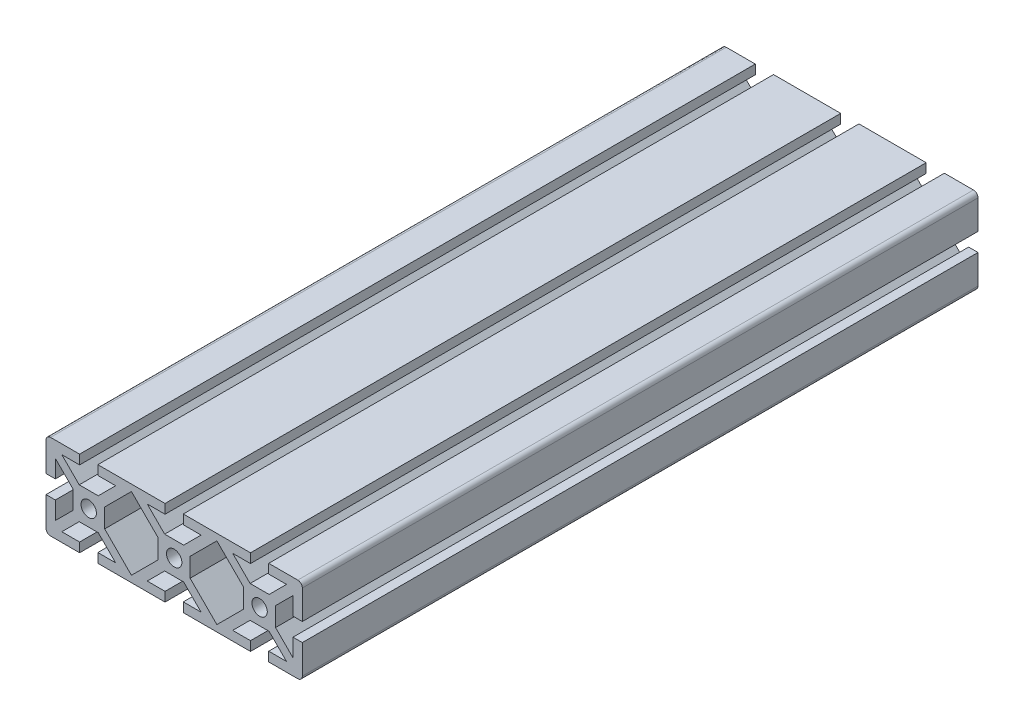
SolidWorks part; units mm, degrees
ref_plane "Front"
ref_plane "Top" through (0, 0, 0) normal (0, 1, 0) x (1, 0, 0)
ref_plane "Right" through (0, 0, 0) normal (1, 0, 0) x (0, 0, -1)
sketch "Sketch1" plane through (0, 0, 0) normal (0, 0, 1) x (1, 0, 0)
  line L0 (0, 0) -> (0, 23.7337) construction
  line L1 (-34.036, -19.05) -> (-34.036, -14.8844)
  line L2 (-45.212, -4.2383) -> (-45.212, 4.2383)
  line L3 (-45.212, 4.2383) -> (-52.9844, 12.0107)
  line L4 (-52.9844, 4.064) -> (-52.9844, 12.0107)
  line L5 (-55.118, 19.05) -> (-42.164, 19.05)
  line L6 (-57.15, 4.064) -> (-57.15, 17.018)
  line L7 (-33.8617, 7.112) -> (-42.3383, 7.112)
  line L8 (-42.3383, 7.112) -> (-50.1107, 14.8844)
  line L9 (-50.1107, 14.8844) -> (-42.164, 14.8844)
  line L10 (-33.8617, 7.112) -> (-26.0893, 14.8844)
  line L11 (-26.0893, 14.8844) -> (-34.036, 14.8844)
  line L12 (-42.164, 19.05) -> (-42.164, 14.8844)
  line L13 (-4.064, 19.05) -> (-34.036, 19.05)
  line L14 (-7.112, 4.2383) -> (-19.05, 16.1763)
  line L15 (-30.988, 4.2383) -> (-19.05, 16.1763)
  line L16 (4.2383, 7.112) -> (-4.2383, 7.112)
  line L17 (-30.988, 4.2383) -> (-30.988, -4.2383)
  line L18 (0, 0) -> (-57.3277, 0) construction
  line L19 (-52.9844, -4.064) -> (-57.15, -4.064)
  line L20 (-4.2383, 7.112) -> (-12.0107, 14.8844)
  line L21 (-4.064, -19.05) -> (-4.064, -14.8844)
  line L22 (-12.0107, 14.8844) -> (-4.064, 14.8844)
  line L23 (-12.0107, -14.8844) -> (-4.064, -14.8844)
  line L24 (-4.2383, -7.112) -> (-12.0107, -14.8844)
  line L25 (4.2383, -7.112) -> (-4.2383, -7.112)
  line L26 (-30.988, -4.2383) -> (-19.05, -16.1763)
  line L27 (-7.112, -4.2383) -> (-19.05, -16.1763)
  line L28 (-4.064, -19.05) -> (-34.036, -19.05)
  line L29 (-42.164, -19.05) -> (-42.164, -14.8844)
  line L30 (-26.0893, -14.8844) -> (-34.036, -14.8844)
  line L31 (-33.8617, -7.112) -> (-26.0893, -14.8844)
  line L32 (-50.1107, -14.8844) -> (-42.164, -14.8844)
  line L33 (-42.3383, -7.112) -> (-50.1107, -14.8844)
  line L34 (-33.8617, -7.112) -> (-42.3383, -7.112)
  line L35 (-4.064, 19.05) -> (-4.064, 14.8844)
  line L36 (-57.15, -4.064) -> (-57.15, -17.018)
  line L37 (-7.112, 4.2383) -> (-7.112, -4.2383)
  line L38 (-55.118, -19.05) -> (-42.164, -19.05)
  line L39 (-52.9844, -4.064) -> (-52.9844, -12.0107)
  line L40 (-45.212, -4.2383) -> (-52.9844, -12.0107)
  line L41 (34.036, 19.05) -> (34.036, 14.8844)
  line L42 (52.9844, 4.064) -> (57.15, 4.064)
  line L43 (45.212, -4.2383) -> (52.9844, -12.0107)
  line L44 (52.9844, -4.064) -> (52.9844, -12.0107)
  line L45 (55.118, -19.05) -> (42.164, -19.05)
  line L46 (7.112, 4.2383) -> (7.112, -4.2383)
  line L47 (57.15, -4.064) -> (57.15, -17.018)
  line L48 (4.064, 19.05) -> (4.064, 14.8844)
  line L49 (33.8617, -7.112) -> (42.3383, -7.112)
  line L50 (42.3383, -7.112) -> (50.1107, -14.8844)
  line L51 (50.1107, -14.8844) -> (42.164, -14.8844)
  line L52 (33.8617, -7.112) -> (26.0893, -14.8844)
  line L53 (26.0893, -14.8844) -> (34.036, -14.8844)
  line L54 (42.164, -19.05) -> (42.164, -14.8844)
  line L55 (4.064, -19.05) -> (34.036, -19.05)
  line L56 (7.112, -4.2383) -> (19.05, -16.1763)
  line L57 (30.988, -4.2383) -> (19.05, -16.1763)
  line L58 (4.2383, -7.112) -> (12.0107, -14.8844)
  line L59 (12.0107, -14.8844) -> (4.064, -14.8844)
  line L60 (-52.9844, 4.064) -> (-57.15, 4.064)
  line L61 (-34.036, 19.05) -> (-34.036, 14.8844)
  line L62 (12.0107, 14.8844) -> (4.064, 14.8844)
  line L63 (4.064, -19.05) -> (4.064, -14.8844)
  line L64 (4.2383, 7.112) -> (12.0107, 14.8844)
  line L65 (52.9844, -4.064) -> (57.15, -4.064)
  line L66 (30.988, 4.2383) -> (30.988, -4.2383)
  line L67 (30.988, 4.2383) -> (19.05, 16.1763)
  line L68 (7.112, 4.2383) -> (19.05, 16.1763)
  line L69 (4.064, 19.05) -> (34.036, 19.05)
  line L70 (42.164, 19.05) -> (42.164, 14.8844)
  line L71 (26.0893, 14.8844) -> (34.036, 14.8844)
  line L72 (33.8617, 7.112) -> (26.0893, 14.8844)
  line L73 (50.1107, 14.8844) -> (42.164, 14.8844)
  line L74 (42.3383, 7.112) -> (50.1107, 14.8844)
  line L75 (33.8617, 7.112) -> (42.3383, 7.112)
  line L76 (57.15, 4.064) -> (57.15, 17.018)
  line L77 (55.118, 19.05) -> (42.164, 19.05)
  line L78 (52.9844, 4.064) -> (52.9844, 12.0107)
  line L79 (45.212, 4.2383) -> (52.9844, 12.0107)
  line L80 (45.212, -4.2383) -> (45.212, 4.2383)
  line L81 (34.036, -19.05) -> (34.036, -14.8844)
  arc A0 (-55.118, 19.05) -> (-57.15, 17.018) centre (-55.118, 17.018) ccw
  arc A1 (-55.118, -19.05) -> (-57.15, -17.018) centre (-55.118, -17.018) cw
  circle A2 centre (38.1, 0) radius 3.429
  arc A3 (55.118, -19.05) -> (57.15, -17.018) centre (55.118, -17.018) ccw
  circle A4 centre (-38.1, 0) radius 3.429
  circle A5 centre (0, 0) radius 3.429
  arc A6 (55.118, 19.05) -> (57.15, 17.018) centre (55.118, 17.018) cw
  point P31 (-7.112, 0)
  point P36 (0, 7.112)
  point P39 (-30.988, 0)
  point P40 (0, 7.112)
  point P50 (-45.212, 0)
  point P66 (-7.112, 0)
  point P85 (0, -7.112)
  point P89 (-30.988, 0)
  point P91 (0, 7.112)
  point P99 (-45.212, 0)
  point P107 (45.212, 0)
  point P108 (30.988, 0)
  point P109 (7.112, 0)
  dimension "D2" = 4.064
  dimension "D5" = 57.15
  dimension "D6" = 45
  dimension "D13" = 4.1656
  dimension "D15" = 4.2383
  dimension "D4" = 42.164
  dimension "D11" = 45.212
  dimension "D12" = 4.1656
  dimension "D14" = 4.2383
  dimension "D3" = 34.036
  dimension "D22" = 2.032
  dimension "D24" = 6.858
  dimension "D1" = 19.05
  dimension "D7" = 45
  dimension "D8" = 45
  dimension "D9" = 7.112
  dimension "D10" = 30.988
  dimension "D16" = 11.938
  dimension "D17" = 4.064
  dimension "D18" = 4.064
  dimension "D19" = 4.064
  dimension "D20" = 4.2383
  dimension "D21" = 14.986
  dimension "D23" = 38.1
extrude "FinalCut" add sketch "Sketch1" against normal blind 301.3074
ref_plane "A" through (0, 0, 0) normal (0, 0, 1) x (1, 0, 0)
ref_plane "B" through (0, 0, -301.3074) normal (0, 0, -1) x (-1, 0, 0)
ref_plane "Y+" through (0, 19.05, 0) normal (0, 1, 0) x (-1, 0, 0)
ref_plane "X+" through (57.15, 0, 0) normal (1, 0, 0) x (0, 0, -1)
ref_plane "Y-" through (0, -19.05, 0) normal (0, -1, 0) x (1, 0, 0)
ref_plane "X-" through (-57.15, 0, 0) normal (-1, 0, 0) x (0, 0, 1)
ref_plane "Slot-1-7-" through (-38.1, 0, 0) normal (1, 0, 0) x (0, 1, 0)
ref_plane "Slot-2-6-" through (0, 0, 0) normal (1, 0, 0) x (0, 0, -1)
ref_plane "Slot-3-5-" through (38.1, 0, 0) normal (1, 0, 0) x (0, 1, 0)
ref_plane "Slot-4-8-" through (0, 0, 0) normal (0, 1, 0) x (0, 0, -1)
sketch "Sketch2" plane through (0, 19.05, 0) normal (0, 1, 0) x (-1, 0, 0)
  circle A0 centre (38.1, -21.717) radius 10.3124
  dimension "D1" = 38.1
  dimension "D2" = 21.717
  dimension "D3" = 20.6248
extrude "AFA1" [suppressed] cut sketch "Sketch2"
sketch "Sketch59" plane through (0, 19.05, 0) normal (0, 1, 0) x (-1, 0, 0)
  line L0 (4.064, 0) -> (34.036, 0) construction
  circle A0 centre (0, -21.717) radius 10.3124
  dimension "D1" = 20.6248
  dimension "D2" = 21.717
extrude "AFA2" [suppressed] cut sketch "Sketch59"
sketch "Sketch4" plane through (0, 19.05, 0) normal (0, 1, 0) x (-1, 0, 0)
  line L2 (-34.036, 0) -> (-4.064, 0) construction
  circle A0 centre (-38.1, -21.717) radius 10.3124
  dimension "D1" = 38.1
  dimension "D2" = 20.6248
  dimension "D3" = 21.717
extrude "AFA3" [suppressed] cut sketch "Sketch4"
sketch "Sketch5" plane through (57.15, 0, 0) normal (1, 0, 0) x (0, 0, -1)
  circle A0 centre (21.717, 0) radius 10.3124
  dimension "D1" = 20.6248
  dimension "D2" = 21.717
extrude "AFA4" [suppressed] cut sketch "Sketch5"
sketch "Sketch7" plane through (0, -19.05, 0) normal (0, -1, 0) x (1, 0, 0)
  circle A0 centre (38.1, -21.717) radius 10.3124
  dimension "D1" = 38.1
  dimension "D2" = 21.717
  dimension "D3" = 20.6248
extrude "AFA5" [suppressed] cut sketch "Sketch7"
sketch "Sketch61" plane through (0, -19.05, 0) normal (0, -1, 0) x (1, 0, 0)
  circle A0 centre (0, -21.717) radius 10.3124
  dimension "D1" = 21.717
  dimension "D2" = 20.6248
extrude "AFA6" [suppressed] cut sketch "Sketch61"
sketch "Sketch8" plane through (0, -19.05, 0) normal (0, -1, 0) x (1, 0, 0)
  circle A0 centre (-38.1, -21.717) radius 10.3124
  dimension "D1" = 38.1
  dimension "D2" = 21.717
  dimension "D3" = 20.6248
extrude "AFA7" [suppressed] cut sketch "Sketch8"
sketch "Sketch10" plane through (-57.15, 0, 0) normal (-1, 0, 0) x (0, 0, 1)
  circle A0 centre (-21.717, 0) radius 10.3124
  dimension "D1" = 21.717
  dimension "D2" = 20.6248
extrude "AFA8" [suppressed] cut sketch "Sketch10"
sketch "Sketch12" plane through (0, 19.05, 0) normal (0, 1, 0) x (-1, 0, 0)
  line L1 (4.064, -301.3074) -> (34.036, -301.3074) construction
  circle A0 centre (38.1, -279.5904) radius 10.3124
  dimension "D1" = 21.717
  dimension "D2" = 38.1
  dimension "D3" = 20.6248
extrude "AFB1" [suppressed] cut sketch "Sketch12"
sketch "Sketch60" plane through (0, 19.05, 0) normal (0, 1, 0) x (-1, 0, 0)
  line L0 (4.064, -301.3074) -> (34.036, -301.3074) construction
  circle A0 centre (0, -279.5904) radius 10.3124
  dimension "D1" = 20.6248
  dimension "D2" = 21.717
extrude "AFB2" [suppressed] cut sketch "Sketch60"
sketch "Sketch11" plane through (0, 19.05, 0) normal (0, 1, 0) x (-1, 0, 0)
  line L1 (-34.036, -301.3074) -> (-4.064, -301.3074) construction
  circle A0 centre (-38.1, -279.5904) radius 10.3124
  dimension "D1" = 38.1
  dimension "D2" = 20.6248
  dimension "D3" = 21.717
extrude "AFB3" [suppressed] cut sketch "Sketch11"
sketch "Sketch14" plane through (57.15, 0, 0) normal (1, 0, 0) x (0, 0, -1)
  line L7 (301.3074, -17.018) -> (301.3074, -4.064) construction
  circle A0 centre (279.5904, 0) radius 10.3124
  dimension "D1" = 21.717
  dimension "D2" = 20.6248
extrude "AFB4" [suppressed] cut sketch "Sketch14"
sketch "Sketch15" plane through (0, -19.05, 0) normal (0, -1, 0) x (1, 0, 0)
  line L1 (4.064, -301.3074) -> (34.036, -301.3074) construction
  circle A0 centre (38.1, -279.5904) radius 10.3124
  dimension "D1" = 21.717
  dimension "D2" = 38.1
  dimension "D3" = 20.6248
extrude "AFB5" [suppressed] cut sketch "Sketch15"
sketch "Sketch62" plane through (0, -19.05, 0) normal (0, -1, 0) x (1, 0, 0)
  line L0 (4.064, -301.3074) -> (34.036, -301.3074) construction
  circle A0 centre (0, -279.5904) radius 10.3124
  dimension "D1" = 20.6248
  dimension "D2" = 21.717
extrude "AFB6" [suppressed] cut sketch "Sketch62"
sketch "Sketch16" plane through (0, -19.05, 0) normal (0, -1, 0) x (1, 0, 0)
  line L1 (-34.036, -301.3074) -> (-4.064, -301.3074) construction
  circle A0 centre (-38.1, -279.5904) radius 10.3124
  dimension "D1" = 21.717
  dimension "D2" = 38.1
  dimension "D3" = 20.6248
extrude "AFB7" [suppressed] cut sketch "Sketch16"
sketch "Sketch17" plane through (-57.15, 0, 0) normal (-1, 0, 0) x (0, 0, 1)
  line L1 (-301.3074, 17.018) -> (-301.3074, 4.064) construction
  circle A0 centre (-279.5904, 0) radius 10.3124
  dimension "D1" = 21.717
  dimension "D2" = 20.6248
extrude "AFB8" [suppressed] cut sketch "Sketch17"
sketch "Sketch20" plane through (0, 19.05, 0) normal (0, 1, 0) x (-1, 0, 0)
  line L1 (4.064, 0) -> (34.036, 0) construction
  circle A0 centre (38.1, -18.3134) radius 10.3124
  dimension "D1" = 18.3134
  dimension "D2" = 20.6248
  dimension "D3" = 38.1
extrude "BFA1" [suppressed] cut sketch "Sketch20"
sketch "Sketch63" plane through (0, 19.05, 0) normal (0, 1, 0) x (-1, 0, 0)
  line L1 (4.064, 0) -> (34.036, 0) construction
  circle A0 centre (0, -18.3134) radius 10.3124
  dimension "D1" = 18.3134
  dimension "D2" = 20.6248
extrude "BFA2" [suppressed] cut sketch "Sketch63"
sketch "Sketch18" plane through (0, 19.05, 0) normal (0, 1, 0) x (-1, 0, 0)
  circle A0 centre (-38.1, -18.3134) radius 10.3124
  dimension "D1" = 38.1
  dimension "D2" = 18.3134
  dimension "D3" = 20.6248
extrude "BFA3" [suppressed] cut sketch "Sketch18"
sketch "Sketch21" plane through (57.15, 0, 0) normal (1, 0, 0) x (0, 0, -1)
  circle A0 centre (18.3134, 0) radius 10.3124
  dimension "D1" = 18.3134
  dimension "D2" = 20.6248
extrude "BFA4" [suppressed] cut sketch "Sketch21"
sketch "Sketch22" plane through (0, -19.05, 0) normal (0, -1, 0) x (1, 0, 0)
  circle A0 centre (38.1, -18.3134) radius 10.3124
  dimension "D2" = 38.1
  dimension "D3" = 20.6248
  dimension "D1" = 18.3134
extrude "BFA5" [suppressed] cut sketch "Sketch22"
sketch "Sketch65" plane through (0, -19.05, 0) normal (0, -1, 0) x (1, 0, 0)
  circle A0 centre (0, -18.3134) radius 10.3124
  dimension "D1" = 20.6248
  dimension "D2" = 18.3134
extrude "BFA6" [suppressed] cut sketch "Sketch65"
sketch "Sketch23" plane through (0, -19.05, 0) normal (0, -1, 0) x (1, 0, 0)
  line L1 (-34.036, 0) -> (-4.064, 0) construction
  circle A0 centre (-38.1, -18.3134) radius 10.3124
  dimension "D1" = 18.3134
  dimension "D2" = 20.6248
  dimension "D3" = 38.1
extrude "BFA7" [suppressed] cut sketch "Sketch23"
sketch "Sketch24" plane through (-57.15, 0, 0) normal (-1, 0, 0) x (0, 0, 1)
  circle A0 centre (-18.3134, 0) radius 10.3124
  dimension "D1" = 18.3134
  dimension "D2" = 20.6248
extrude "BFA8" [suppressed] cut sketch "Sketch24"
sketch "Sketch27" plane through (0, 19.05, 0) normal (0, 1, 0) x (-1, 0, 0)
  line L1 (4.064, -301.3074) -> (34.036, -301.3074) construction
  circle A0 centre (38.1, -282.994) radius 10.3124
  dimension "D1" = 38.1
  dimension "D2" = 20.6248
  dimension "D3" = 18.3134
extrude "BFB1" [suppressed] cut sketch "Sketch27"
sketch "Sketch64" plane through (0, 19.05, 0) normal (0, 1, 0) x (-1, 0, 0)
  line L0 (4.064, -301.3074) -> (34.036, -301.3074) construction
  circle A0 centre (0, -282.994) radius 10.3124
  dimension "D1" = 20.6248
  dimension "D2" = 18.3134
extrude "BFB2" [suppressed] cut sketch "Sketch64"
sketch "Sketch25" plane through (0, 19.05, 0) normal (0, 1, 0) x (-1, 0, 0)
  line L1 (-34.036, -301.3074) -> (-4.064, -301.3074) construction
  circle A0 centre (-38.1, -282.994) radius 10.3124
  dimension "D1" = 18.3134
  dimension "D2" = 38.1
  dimension "D3" = 20.6248
extrude "BFB3" [suppressed] cut sketch "Sketch25"
sketch "Sketch29" plane through (57.15, 0, 0) normal (1, 0, 0) x (0, 0, -1)
  line L1 (301.3074, -17.018) -> (301.3074, -4.064) construction
  circle A0 centre (282.994, 0) radius 10.3124
  dimension "D1" = 18.3134
  dimension "D2" = 20.6248
extrude "BFB4" [suppressed] cut sketch "Sketch29"
sketch "Sketch30" plane through (0, -19.05, 0) normal (0, -1, 0) x (1, 0, 0)
  line L1 (4.064, -301.3074) -> (34.036, -301.3074) construction
  circle A0 centre (38.1, -282.994) radius 10.3124
  dimension "D1" = 18.3134
  dimension "D2" = 38.1
  dimension "D3" = 20.6248
extrude "BFB5" [suppressed] cut sketch "Sketch30"
sketch "Sketch66" plane through (0, -19.05, 0) normal (0, -1, 0) x (1, 0, 0)
  line L0 (-4.2383, -301.3074) -> (4.2383, -301.3074) construction
  circle A0 centre (0, -282.994) radius 10.3124
  dimension "D1" = 18.3134
  dimension "D2" = 20.6248
extrude "BFB6" [suppressed] cut sketch "Sketch66"
sketch "Sketch31" plane through (0, -19.05, 0) normal (0, -1, 0) x (1, 0, 0)
  line L1 (4.064, -301.3074) -> (34.036, -301.3074) construction
  circle A0 centre (-38.1, -282.994) radius 10.3124
  dimension "D1" = 18.3134
  dimension "D2" = 38.1
  dimension "D3" = 20.6248
extrude "BFB7" [suppressed] cut sketch "Sketch31"
sketch "Sketch32" plane through (-57.15, 0, 0) normal (-1, 0, 0) x (0, 0, 1)
  line L5 (-301.3074, -4.064) -> (-301.3074, -17.018) construction
  circle A0 centre (-282.994, 0) radius 10.3124
  dimension "D1" = 18.3134
  dimension "D2" = 20.6248
extrude "BFB8" [suppressed] cut sketch "Sketch32"
sketch "Sketch33" plane through (0, 0, 0) normal (0, 0, 1) x (1, 0, 0)
  circle A0 centre (-38.1, 0) radius 3.937
  circle A1 centre (38.1, 0) radius 3.937
  circle A2 centre (0, 0) radius 3.937
  dimension "D1" = 7.874
extrude "TPA660010" [suppressed] cut sketch "Sketch33"
sketch "Sketch34" plane through (0, 0, -301.3074) normal (0, 0, -1) x (-1, 0, 0)
  circle A0 centre (-38.1, 0) radius 3.937
  circle A1 centre (38.1, 0) radius 3.937
  circle A2 centre (0, 0) radius 3.937
  dimension "D1" = 7.874
extrude "TPB660010" [suppressed] cut sketch "Sketch34"
sketch "Sketch36" plane through (0, 0, 0) normal (0, 0, 1) x (1, 0, 0)
  circle A0 centre (38.1, 0) radius 4.064
  circle A1 centre (-38.1, 0) radius 4.064
  circle A2 centre (0, 0) radius 4.064
  dimension "D1" = 8.128
extrude "TPA660011" [suppressed] cut sketch "Sketch36"
sketch "Sketch37" [suppressed] plane through (0, 0, -101.6) normal (0, 0, -1) x (-1, 0, 0)
  circle A0 centre (38.1, 0) radius 4.064
  circle A1 centre (-38.1, 0) radius 4.064
  circle A2 centre (0, 0) radius 4.064
  dimension "D1" = 8.128
extrude "TPB660011" [suppressed] cut sketch "Sketch37"
sketch "Sketch39" plane through (0, 0, -301.3074) normal (0, 0, -1) x (-1, 0, 0)
  point P0 (0, 0)
sketch "Sketch38" plane through (0, 0, 0) normal (1, 0, 0) x (0, 0, -1)
  line L0 (0, 19.05) -> (38.1, -19.05)
  line L3 (301.3074, 19.05) -> (0, 19.05) construction
  line L4 (301.3074, -19.05) -> (0, -19.05) construction
  dimension "D1" = 45
extrude "MITA1" [suppressed] cut sketch "Sketch38"
ref_plane "AMITA1" through (0, 9.525, -9.525) normal (0, 0.7071, -0.7071) x (-1, 0, 0)
ref_plane "AMITOFFA1" through (0, 14.0151, -14.0151) normal (0, 0.7071, -0.7071) x (-1, 0, 0)
sketch "Sketch43" [suppressed] plane through (0, 14.0151, -14.0151) normal (0, 0.7071, -0.7071) x (-1, 0, 0)
  line L1 (4.064, 13.4704) -> (34.036, 13.4704) construction
  circle A0 centre (-38.1, -15.1046) radius 9.525
  circle A1 centre (38.1, -15.1046) radius 9.525
  circle A2 centre (0, -15.1046) radius 9.525
  dimension "D1" = 19.05
  dimension "D2" = 76.2
  dimension "D3" = 28.575
  dimension "D4" = 38.1
extrude "MITCBA1" [suppressed] cut sketch "Sketch43"
sketch "Sketch44" [suppressed] plane through (0, 14.0151, -14.0151) normal (0, 0.7071, -0.7071) x (-1, 0, 0)
  line L1 (4.064, 13.4704) -> (34.036, 13.4704) construction
  circle A0 centre (-38.1, -15.1046) radius 4.1656
  circle A1 centre (38.1, -15.1046) radius 4.1656
  circle A2 centre (0, -15.1046) radius 4.1656
  dimension "D1" = 76.2
  dimension "D2" = 8.3312
  dimension "D3" = 38.1
  dimension "D4" = 28.575
extrude "MITDRA1" [suppressed] cut sketch "Sketch44"
sketch "Sketch45" [suppressed] plane through (0, 14.0151, -14.0151) normal (0, 0.7071, -0.7071) x (-1, 0, 0)
  line L0 (-47.625, 13.4704) -> (-47.625, -4.0048)
  line L1 (-28.575, -4.0048) -> (-28.575, 13.4704)
  line L2 (-28.575, 13.4704) -> (-47.625, 13.4704)
  line L3 (28.575, 13.4704) -> (28.575, -4.0048)
  line L4 (47.625, -4.0048) -> (47.625, 13.4704)
  line L5 (47.625, 13.4704) -> (28.575, 13.4704)
  line L7 (-34.036, 13.4704) -> (-4.064, 13.4704) construction
  line L8 (-9.525, 13.4704) -> (9.525, 13.4704)
  line L9 (-9.525, 13.4704) -> (-9.525, -4.0048)
  line L10 (9.525, -4.0048) -> (9.525, 13.4704)
  arc A0 (-47.625, -4.0048) -> (-28.575, -4.0048) centre (-38.1, -4.0048) ccw
  arc A1 (28.575, -4.0048) -> (47.625, -4.0048) centre (38.1, -4.0048) ccw
  arc A2 (-9.525, -4.0048) -> (9.525, -4.0048) centre (0, -4.0048) ccw
  dimension "D1" = 17.4752
  dimension "D2" = 9.525
  dimension "D3" = 76.2
  dimension "D4" = 38.1
extrude "MITEBA1" [suppressed] cut sketch "Sketch45"
sketch "Sketch46" [suppressed] plane through (0, 14.0151, -14.0151) normal (0, 0.7071, -0.7071) x (-1, 0, 0)
  line L0 (-42.2656, 13.4704) -> (-42.2656, -4.0048)
  line L1 (-33.9344, -4.0048) -> (-33.9344, 13.4704)
  line L2 (-33.9344, 13.4704) -> (-42.2656, 13.4704)
  line L3 (33.9344, 13.4704) -> (33.9344, -4.0048)
  line L4 (42.2656, -4.0048) -> (42.2656, 13.4704)
  line L5 (42.2656, 13.4704) -> (33.9344, 13.4704)
  line L6 (4.064, 13.4704) -> (34.036, 13.4704) construction
  line L7 (-34.036, 13.4704) -> (-4.064, 13.4704) construction
  line L8 (-4.1656, 13.4704) -> (-4.1656, -4.0048)
  line L9 (4.1656, -4.0048) -> (4.1656, 13.4704)
  line L10 (4.1656, 13.4704) -> (-4.1656, 13.4704)
  arc A0 (-42.2656, -4.0048) -> (-33.9344, -4.0048) centre (-38.1, -4.0048) ccw
  arc A1 (33.9344, -4.0048) -> (42.2656, -4.0048) centre (38.1, -4.0048) ccw
  arc A2 (-4.1656, -4.0048) -> (4.1656, -4.0048) centre (0, -4.0048) ccw
  dimension "D2" = 4.1656
  dimension "D3" = 76.2
  dimension "D4" = 38.1
  dimension "D1" = 17.4752
extrude "MITEDA1" [suppressed] cut sketch "Sketch46"
sketch "Sketch40" plane through (0, 0, 0) normal (1, 0, 0) x (0, 0, -1)
  line L0 (301.3074, 19.05) -> (263.2074, -19.05)
  line L3 (301.3074, 19.05) -> (0, 19.05) construction
  line L4 (301.3074, -19.05) -> (0, -19.05) construction
  dimension "D1" = 45
extrude "MITB1" [suppressed] cut sketch "Sketch40"
ref_plane "AMITB1" through (0, -41.275, -41.275) normal (0, 0.7071, 0.7071) x (1, 0, 0)
ref_plane "AMITOFFB1" through (0, -36.7849, -36.7849) normal (0, 0.7071, 0.7071) x (1, 0, 0)
sketch "Sketch47" [suppressed] plane through (0, -36.7849, -36.7849) normal (0, 0.7071, 0.7071) x (1, 0, 0)
  line L1 (34.036, 85.3124) -> (4.064, 85.3124) construction
  circle A0 centre (-38.1, 56.7374) radius 9.525
  circle A1 centre (38.1, 56.7374) radius 9.525
  circle A2 centre (0, 56.7374) radius 9.525
  dimension "D1" = 19.05
  dimension "D2" = 76.2
  dimension "D3" = 38.1
  dimension "D4" = 28.575
extrude "MITCBB1" [suppressed] cut sketch "Sketch47"
sketch "Sketch48" [suppressed] plane through (0, -36.7849, -36.7849) normal (0, 0.7071, 0.7071) x (1, 0, 0)
  line L1 (34.036, 85.3124) -> (4.064, 85.3124) construction
  circle A0 centre (-38.1, 56.7374) radius 4.1656
  circle A1 centre (38.1, 56.7374) radius 4.1656
  circle A2 centre (0, 56.7374) radius 4.1656
  dimension "D1" = 76.2
  dimension "D2" = 8.3312
  dimension "D3" = 38.1
  dimension "D4" = 28.575
extrude "MITDRB1" [suppressed] cut sketch "Sketch48"
sketch "Sketch49" [suppressed] plane through (0, -36.7849, -36.7849) normal (0, 0.7071, 0.7071) x (1, 0, 0)
  line L0 (-47.625, 85.3124) -> (-47.625, 67.8372)
  line L1 (-28.575, 67.8372) -> (-28.575, 85.3124)
  line L2 (-28.575, 85.3124) -> (-47.625, 85.3124)
  line L3 (28.575, 85.3124) -> (28.575, 67.8372)
  line L4 (47.625, 67.8372) -> (47.625, 85.3124)
  line L5 (47.625, 85.3124) -> (28.575, 85.3124)
  line L7 (34.036, 85.3124) -> (4.064, 85.3124) construction
  line L8 (-9.525, 85.3124) -> (-9.525, 67.8372)
  line L9 (9.525, 67.8372) -> (9.525, 85.3124)
  line L10 (9.525, 85.3124) -> (-9.525, 85.3124)
  arc A0 (-47.625, 67.8372) -> (-28.575, 67.8372) centre (-38.1, 67.8372) ccw
  arc A1 (28.575, 67.8372) -> (47.625, 67.8372) centre (38.1, 67.8372) ccw
  arc A2 (-9.525, 67.8372) -> (9.525, 67.8372) centre (0, 67.8372) ccw
  dimension "D1" = 76.2
  dimension "D2" = 17.4752
  dimension "D3" = 38.1
  dimension "D4" = 9.525
extrude "MITEBB1" [suppressed] cut sketch "Sketch49"
sketch "Sketch50" [suppressed] plane through (0, -36.7849, -36.7849) normal (0, 0.7071, 0.7071) x (1, 0, 0)
  line L0 (-42.2656, 85.3124) -> (-42.2656, 67.8372)
  line L1 (-33.9344, 67.8372) -> (-33.9344, 85.3124)
  line L2 (-33.9344, 85.3124) -> (-42.2656, 85.3124)
  line L3 (33.9344, 85.3124) -> (33.9344, 67.8372)
  line L4 (42.2656, 67.8372) -> (42.2656, 85.3124)
  line L5 (42.2656, 85.3124) -> (33.9344, 85.3124)
  line L7 (-4.064, 85.3124) -> (-34.036, 85.3124) construction
  line L8 (-4.1656, 85.3124) -> (-4.1656, 67.8372)
  line L9 (4.1656, 67.8372) -> (4.1656, 85.3124)
  line L10 (4.1656, 85.3124) -> (-4.1656, 85.3124)
  arc A0 (-42.2656, 67.8372) -> (-33.9344, 67.8372) centre (-38.1, 67.8372) ccw
  arc A1 (33.9344, 67.8372) -> (42.2656, 67.8372) centre (38.1, 67.8372) ccw
  arc A2 (-4.1656, 67.8372) -> (4.1656, 67.8372) centre (0, 67.8372) ccw
  dimension "D1" = 17.4752
  dimension "D2" = 4.1656
  dimension "D3" = 76.2
  dimension "D4" = 38.1
extrude "MITEDB1" [suppressed] cut sketch "Sketch50"
sketch "Sketch41" plane through (0, 0, 0) normal (1, 0, 0) x (0, 0, -1)
  line L0 (0, -19.05) -> (38.1, 19.05)
  line L3 (301.3074, -19.05) -> (0, -19.05) construction
  line L4 (301.3074, 19.05) -> (0, 19.05) construction
  dimension "D1" = 45
extrude "MITA5" [suppressed] cut sketch "Sketch41"
ref_plane "AMITA5" through (0, -9.525, -9.525) normal (0, -0.7071, -0.7071) x (-1, 0, 0)
ref_plane "AMITOFFA5" through (0, -14.0151, -14.0151) normal (0, -0.7071, -0.7071) x (-1, 0, 0)
sketch "Sketch51" [suppressed] plane through (0, -14.0151, -14.0151) normal (0, -0.7071, -0.7071) x (-1, 0, 0)
  line L1 (-4.064, -13.4704) -> (-34.036, -13.4704) construction
  circle A0 centre (-38.1, 15.1046) radius 9.525
  circle A1 centre (38.1, 15.1046) radius 9.525
  circle A2 centre (0, 15.1046) radius 9.525
  dimension "D1" = 76.2
  dimension "D2" = 19.05
  dimension "D3" = 28.575
  dimension "D4" = 38.1
extrude "MITCBA5" [suppressed] cut sketch "Sketch51"
sketch "Sketch52" [suppressed] plane through (0, -14.0151, -14.0151) normal (0, -0.7071, -0.7071) x (-1, 0, 0)
  line L1 (34.036, -13.4704) -> (4.064, -13.4704) construction
  circle A0 centre (-38.1, 15.1046) radius 4.1656
  circle A1 centre (38.1, 15.1046) radius 4.1656
  circle A2 centre (0, 15.1046) radius 4.1656
  dimension "D1" = 28.575
  dimension "D2" = 76.2
  dimension "D3" = 38.1
  dimension "D4" = 8.3312
extrude "MITDRA5" [suppressed] cut sketch "Sketch52"
sketch "Sketch53" [suppressed] plane through (0, -14.0151, -14.0151) normal (0, -0.7071, -0.7071) x (-1, 0, 0)
  line L0 (-47.625, -13.4704) -> (-47.625, 4.0048)
  line L1 (-28.575, 4.0048) -> (-28.575, -13.4704)
  line L2 (-28.575, -13.4704) -> (-47.625, -13.4704)
  line L3 (28.575, -13.4704) -> (28.575, 4.0048)
  line L4 (47.625, 4.0048) -> (47.625, -13.4704)
  line L5 (47.625, -13.4704) -> (28.575, -13.4704)
  line L7 (-42.164, -13.4704) -> (-55.118, -13.4704) construction
  line L8 (-9.525, -13.4704) -> (-9.525, 4.0048)
  line L9 (9.525, 4.0048) -> (9.525, -13.4704)
  line L10 (9.525, -13.4704) -> (-9.525, -13.4704)
  line L11 (-4.064, -13.4704) -> (-34.036, -13.4704) construction
  arc A0 (-47.625, 4.0048) -> (-28.575, 4.0048) centre (-38.1, 4.0048) cw
  arc A1 (28.575, 4.0048) -> (47.625, 4.0048) centre (38.1, 4.0048) cw
  arc A2 (-9.525, 4.0048) -> (9.525, 4.0048) centre (0, 4.0048) cw
  dimension "D1" = 17.4752
  dimension "D2" = 9.525
  dimension "D3" = 76.2
  dimension "D4" = 38.1
extrude "MITEBA5" [suppressed] cut sketch "Sketch53"
sketch "Sketch54" [suppressed] plane through (0, -14.0151, -14.0151) normal (0, -0.7071, -0.7071) x (-1, 0, 0)
  line L0 (-42.2656, -13.4704) -> (-42.2656, 4.0048)
  line L1 (-33.9344, 4.0048) -> (-33.9344, -13.4704)
  line L2 (-33.9344, -13.4704) -> (-42.2656, -13.4704)
  line L3 (33.9344, -13.4704) -> (33.9344, 4.0048)
  line L4 (42.2656, 4.0048) -> (42.2656, -13.4704)
  line L5 (42.2656, -13.4704) -> (33.9344, -13.4704)
  line L7 (-4.064, -13.4704) -> (-34.036, -13.4704) construction
  line L8 (-4.1656, -13.4704) -> (-4.1656, 4.0048)
  line L9 (4.1656, 4.0048) -> (4.1656, -13.4704)
  line L10 (4.1656, -13.4704) -> (-4.1656, -13.4704)
  arc A0 (-42.2656, 4.0048) -> (-33.9344, 4.0048) centre (-38.1, 4.0048) cw
  arc A1 (33.9344, 4.0048) -> (42.2656, 4.0048) centre (38.1, 4.0048) cw
  arc A2 (-4.1656, 4.0048) -> (4.1656, 4.0048) centre (0, 4.0048) cw
  dimension "D1" = 76.2
  dimension "D2" = 17.4752
  dimension "D3" = 38.1
  dimension "D4" = 4.1656
extrude "MITEDA5" [suppressed] cut sketch "Sketch54"
sketch "Sketch42" plane through (0, 0, 0) normal (1, 0, 0) x (0, 0, -1)
  line L0 (301.3074, -19.05) -> (263.2074, 19.05)
  line L3 (301.3074, -19.05) -> (0, -19.05) construction
  line L4 (301.3074, 19.05) -> (0, 19.05) construction
  dimension "D1" = 45
extrude "MITB5" [suppressed] cut sketch "Sketch42"
ref_plane "AMITB5" through (0, 41.275, -41.275) normal (0, -0.7071, 0.7071) x (1, 0, 0)
ref_plane "AMITOFFB5" through (0, 36.7849, -36.7849) normal (0, -0.7071, 0.7071) x (1, 0, 0)
sketch "Sketch55" [suppressed] plane through (0, 36.7849, -36.7849) normal (0, -0.7071, 0.7071) x (1, 0, 0)
  line L1 (4.064, -85.3124) -> (34.036, -85.3124) construction
  circle A0 centre (-38.1, -56.7374) radius 9.525
  circle A1 centre (38.1, -56.7374) radius 9.525
  circle A2 centre (0, -56.7374) radius 9.525
  dimension "D1" = 28.575
  dimension "D2" = 19.05
  dimension "D3" = 76.2
  dimension "D4" = 38.1
extrude "MITCBB5" [suppressed] cut sketch "Sketch55"
sketch "Sketch56" [suppressed] plane through (0, 36.7849, -36.7849) normal (0, -0.7071, 0.7071) x (1, 0, 0)
  line L1 (4.064, -85.3124) -> (34.036, -85.3124) construction
  circle A0 centre (-38.1, -56.7374) radius 4.1656
  circle A1 centre (38.1, -56.7374) radius 4.1656
  circle A2 centre (0, -56.7374) radius 4.1656
  dimension "D1" = 76.2
  dimension "D2" = 8.3312
  dimension "D3" = 38.1
  dimension "D4" = 28.575
extrude "MITDRB5" [suppressed] cut sketch "Sketch56"
sketch "Sketch57" [suppressed] plane through (0, 36.7849, -36.7849) normal (0, -0.7071, 0.7071) x (1, 0, 0)
  line L0 (-47.625, -85.3124) -> (-47.625, -67.8372)
  line L1 (-28.575, -67.8372) -> (-28.575, -85.3124)
  line L2 (-28.575, -85.3124) -> (-47.625, -85.3124)
  line L3 (28.575, -85.3124) -> (28.575, -67.8372)
  line L4 (47.625, -67.8372) -> (47.625, -85.3124)
  line L5 (47.625, -85.3124) -> (28.575, -85.3124)
  line L7 (-55.118, -85.3124) -> (-42.164, -85.3124) construction
  line L8 (-9.525, -85.3124) -> (-9.525, -67.8372)
  line L9 (9.525, -67.8372) -> (9.525, -85.3124)
  line L10 (9.525, -85.3124) -> (-9.525, -85.3124)
  arc A0 (-47.625, -67.8372) -> (-28.575, -67.8372) centre (-38.1, -67.8372) cw
  arc A1 (28.575, -67.8372) -> (47.625, -67.8372) centre (38.1, -67.8372) cw
  arc A2 (-9.525, -67.8372) -> (9.525, -67.8372) centre (0, -67.8372) cw
  dimension "D1" = 76.2
  dimension "D2" = 9.525
  dimension "D3" = 17.4752
  dimension "D4" = 38.1
extrude "MITEBB5" [suppressed] cut sketch "Sketch57"
sketch "Sketch58" [suppressed] plane through (0, 36.7849, -36.7849) normal (0, -0.7071, 0.7071) x (1, 0, 0)
  line L0 (-42.2656, -85.3124) -> (-42.2656, -67.8372)
  line L1 (-33.9344, -67.8372) -> (-33.9344, -85.3124)
  line L2 (-33.9344, -85.3124) -> (-42.2656, -85.3124)
  line L3 (33.9344, -85.3124) -> (33.9344, -67.8372)
  line L4 (42.2656, -67.8372) -> (42.2656, -85.3124)
  line L5 (42.2656, -85.3124) -> (33.9344, -85.3124)
  line L7 (-34.036, -85.3124) -> (-4.064, -85.3124) construction
  line L8 (-4.1656, -85.3124) -> (-4.1656, -67.8372)
  line L9 (4.1656, -67.8372) -> (4.1656, -85.3124)
  line L10 (4.1656, -85.3124) -> (-4.1656, -85.3124)
  arc A0 (-42.2656, -67.8372) -> (-33.9344, -67.8372) centre (-38.1, -67.8372) cw
  arc A1 (33.9344, -67.8372) -> (42.2656, -67.8372) centre (38.1, -67.8372) cw
  arc A2 (-4.1656, -67.8372) -> (4.1656, -67.8372) centre (0, -67.8372) cw
  dimension "D1" = 4.1656
  dimension "D2" = 76.2
  dimension "D4" = 38.1
  dimension "D3" = 17.4752
extrude "MITEDB5" [suppressed] cut sketch "Sketch58"
